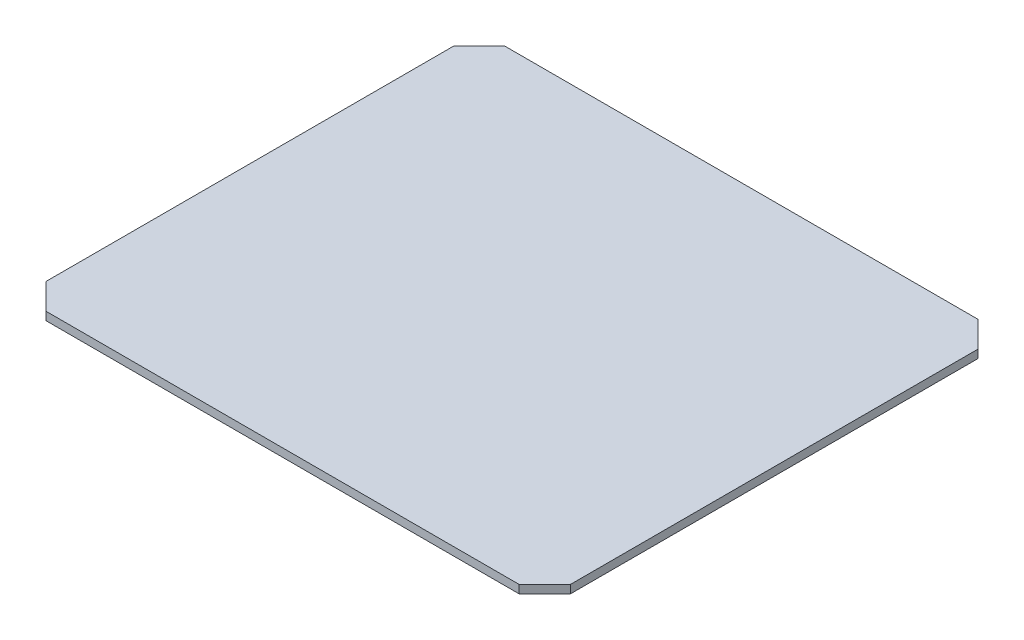
SolidWorks part; units mm, degrees
material "6061 Alloy"
ref_plane "Front" through (0, 0, 0) normal (0, 0, 1) x (1, 0, 0)
ref_plane "Top" through (0, 0, 0) normal (0, 1, 0) x (1, 0, 0)
ref_plane "Right" through (0, 0, 0) normal (1, 0, 0) x (0, 0, -1)
ref_axis "Axis1" through (0, 0, 55) along (0, 0, -1)
sketch "Sketch1" plane through (0, 0, 0) normal (0, 1, 0) x (1, 0, 0)
  line L1 (-101.6, 88.9) -> (101.6, 88.9)
  line L2 (-101.6, 88.9) -> (-101.6, -88.9)
  line L3 (-101.6, -88.9) -> (101.6, -88.9)
  line L4 (101.6, 88.9) -> (101.6, -88.9)
  line L5 (-101.6, 88.9) -> (101.6, -88.9) construction
  line L6 (-101.6, -88.9) -> (101.6, 88.9) construction
  point P0 (0, 0)
  dimension "D1" = 177.8
  dimension "D2" = 203.2
extrude "Boss-Extrude1" add sketch "Sketch1" along normal blind 3.175
chamfer "Chamfer1" distance 10 angle 45 4 edges at (-101.6, 1.5875, -88.9) (101.6, 1.5875, -88.9) (101.6, 1.5875, 88.9) (-101.6, 1.5875, 88.9)
